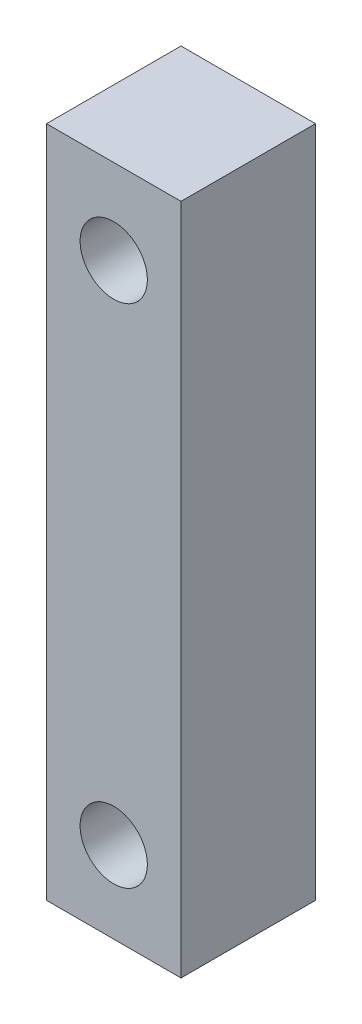
SolidWorks part; units mm, degrees
ref_plane "Front Plane" through (0, 0, 0) normal (0, 0, 1) x (1, 0, 0)
ref_plane "Top Plane" through (0, 0, 0) normal (0, 1, 0) x (1, 0, 0)
ref_plane "Right Plane" through (0, 0, 0) normal (1, 0, 0) x (0, 0, -1)
sketch "Sketch1" plane through (0, 0, 0) normal (0, 1, 0) x (1, 0, 0)
  line L1 (-12.7, -12.7) -> (12.7, -12.7)
  line L2 (-12.7, -12.7) -> (-12.7, 12.7)
  line L3 (-12.7, 12.7) -> (12.7, 12.7)
  line L4 (12.7, -12.7) -> (12.7, 12.7)
  line L5 (-12.7, -12.7) -> (12.7, 12.7) construction
  line L6 (-12.7, 12.7) -> (12.7, -12.7) construction
  point P0 (0, 0)
  dimension "D1" = 25.4
  dimension "D2" = 25.4
extrude "Boss-Extrude1" add sketch "Sketch1" along normal mid plane 127
sketch "Sketch2" plane through (0, 0, 12.7) normal (0, 0, 1) x (1, 0, 0)
  circle A0 centre (0, 47.4882) radius 6.35
  circle A1 centre (0, -48.1117) radius 6.35
  dimension "D1" = 12.7
  dimension "D2" = 12.7
extrude "Cut-Extrude1" cut sketch "Sketch2" against normal blind 127
